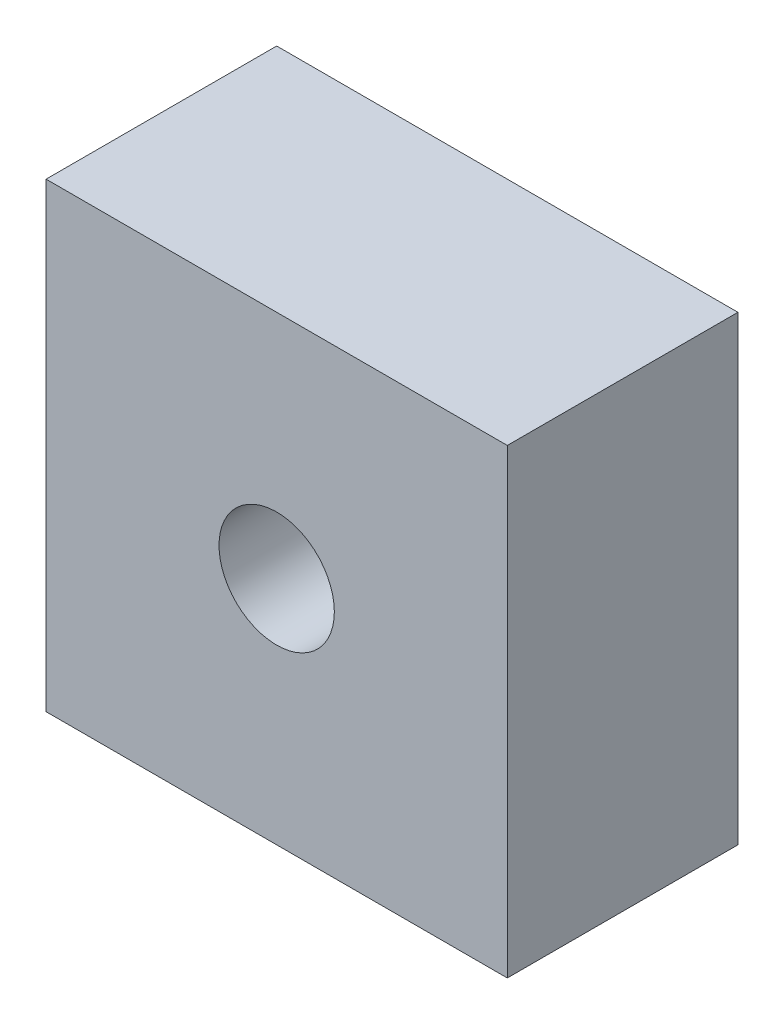
SolidWorks part; units mm, degrees
material "1060 Alloy"
ref_plane "Front Plane" through (0, 0, 0) normal (0, 0, 1) x (1, 0, 0)
ref_plane "Top Plane" through (0, 0, 0) normal (0, 1, 0) x (1, 0, 0)
ref_plane "Right Plane" through (0, 0, 0) normal (1, 0, 0) x (0, 0, -1)
sketch "Sketch1" plane through (0, 0, 0) normal (0, 0, 1) x (1, 0, 0)
  line L1 (-6.35, -6.35) -> (6.35, -6.35)
  line L2 (-6.35, -6.35) -> (-6.35, 6.35)
  line L3 (-6.35, 6.35) -> (6.35, 6.35)
  line L4 (6.35, -6.35) -> (6.35, 6.35)
  line L5 (-6.35, -6.35) -> (6.35, 6.35) construction
  line L6 (-6.35, 6.35) -> (6.35, -6.35) construction
  circle A0 centre (0, 0) radius 1.5875
  point P0 (0, 0)
  dimension "D2" = 3.175
  dimension "D1" = 12.7
extrude "Boss-Extrude1" add sketch "Sketch1" along normal blind 6.35
